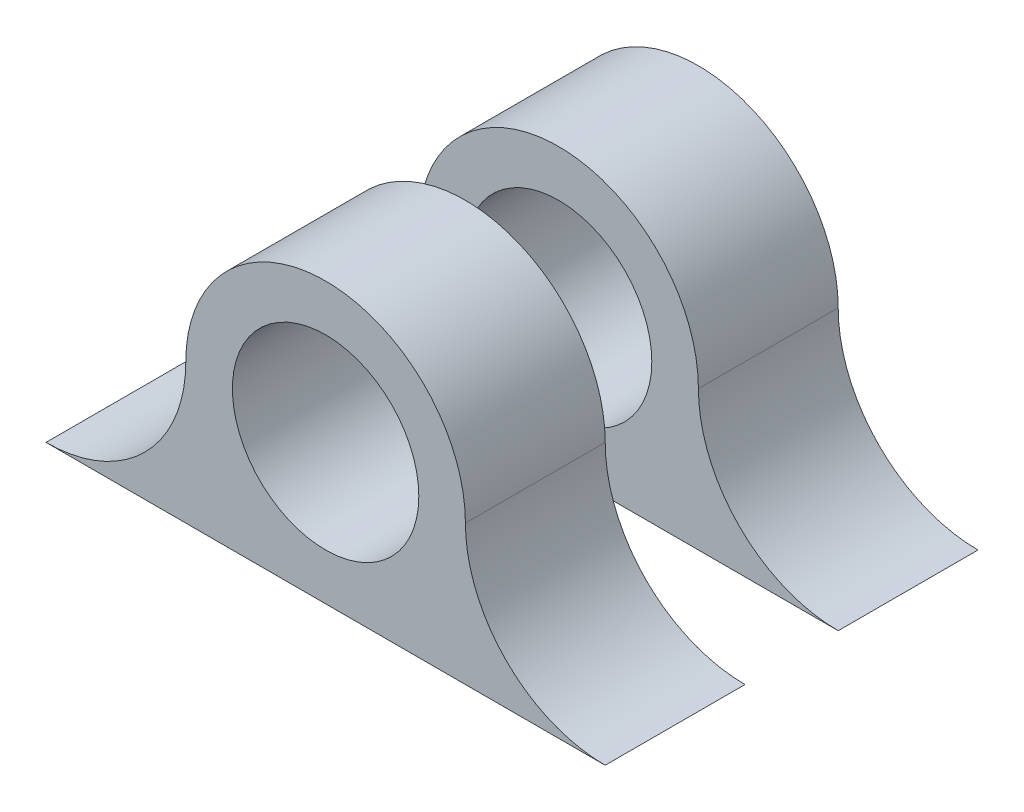
SolidWorks part; units mm, degrees
ref_plane "前基準面" through (0, 0, 0) normal (0, 0, 1) x (1, 0, 0)
ref_plane "上基準面" through (0, 0, 0) normal (0, 1, 0) x (1, 0, 0)
ref_plane "右基準面" through (0, 0, 0) normal (1, 0, 0) x (0, 0, -1)
sketch "草圖2" plane through (0, 0, 0) normal (0, 0, 1) x (1, 0, 0)
  line L0 (3.5, 5) -> (6.5, 5)
  circle A0 centre (5, 5.75) radius 0.5
  arc A1 (5.75, 5.75) -> (4.25, 5.75) centre (5, 5.75) ccw
  arc A2 (3.5, 5) -> (4.25, 5.75) centre (3.5, 5.75) ccw
  arc A3 (5.75, 5.75) -> (6.5, 5) centre (6.5, 5.75) ccw
extrude "填料-伸長4" add sketch "草圖2" along normal blind 1 and the other way blind 1
extrude "除料-伸長2" cut sketch "草圖2<7>" against normal blind 0.25 and the other way blind 0.25
sketch "草圖2<7>" plane through (0, 0, 0) normal (0, 0, 1) x (1, 0, 0) same geometry as "草圖2"
